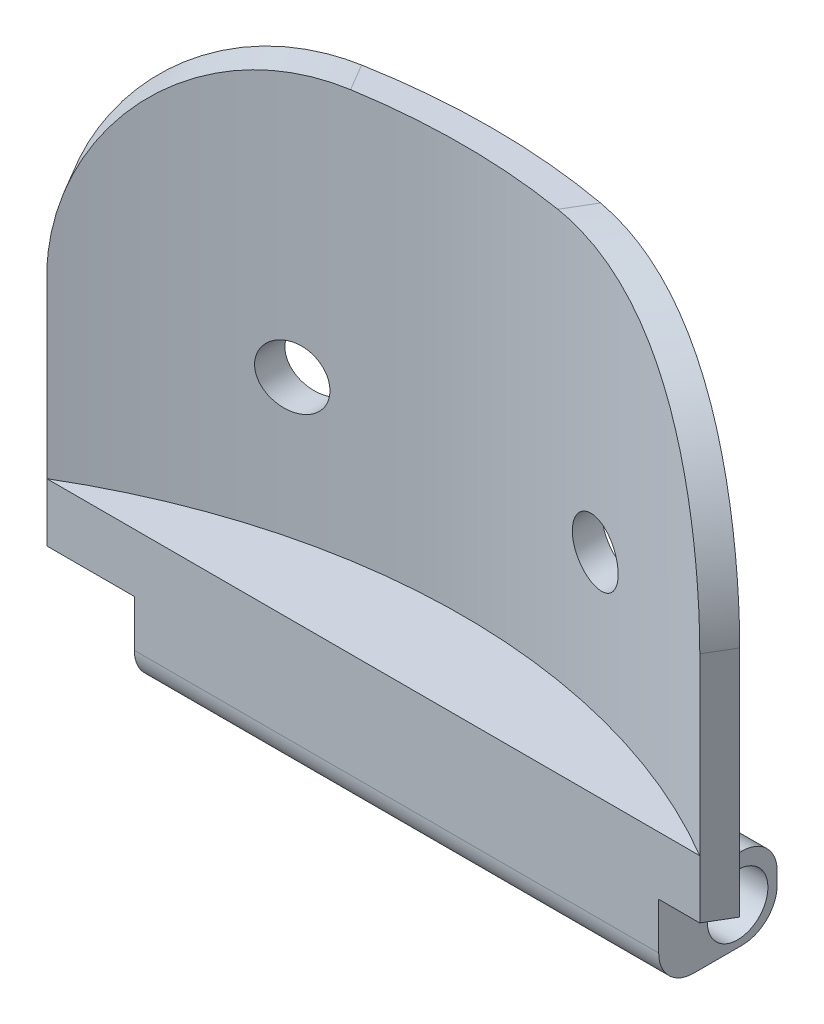
SolidWorks part; units mm, degrees
ref_plane "Front Plane" through (0, 0, 0) normal (0, 0, 1) x (1, 0, 0)
ref_plane "Top Plane" through (0, 0, 0) normal (0, 1, 0) x (1, 0, 0)
ref_plane "Right Plane" through (0, 0, 0) normal (1, 0, 0) x (0, 0, -1)
sketch "Sketch1" plane through (0, 0, 0) normal (0, 1, 0) x (1, 0, 0)
  line L2 (-37.2024, 62.8381) -> (-35.585, 60.106)
  line L3 (37.2024, 62.8381) -> (35.585, 60.106)
  circle A0 centre (0, 0) radius 73.025
  circle A1 centre (0, 0) radius 69.85
  point P7 (0, 62.8381)
extrude "Boss-Extrude1" add sketch "Sketch1" along normal blind 50.8 contours A1 L3 A0 L2 region at (0, 0, -72.2698)
fillet "Fillet1" radius 25.4 2 edges at (-36.3937, 50.8, -61.4721) (36.3937, 50.8, -61.4721)
sketch "Sketch2" plane through (0, 0, 0) normal (0, -1, 0) x (1, 0, 0)
  line L0 (0, -73.025) -> (0, -65.405) construction
  line L1 (25.4114, -73.025) -> (-25.3886, -73.025) construction
  line L2 (-25.3886, -73.025) -> (25.4114, -73.025)
  line L3 (-25.3886, -73.025) -> (-25.3886, -64.135)
  line L4 (25.4114, -73.025) -> (25.4114, -64.135)
  line L5 (-25.3886, -64.135) -> (25.4114, -64.135)
  arc A0 (-37.2024, -62.8381) -> (37.2024, -62.8381) centre (0, 0) ccw construction
  point P8 (0.0114, -73.025)
ref_plane "Plane1" through (0, 0, -73.025) normal (0, 0, -1) x (-1, 0, 0)
sketch "Sketch5" plane through (0, 0, -73.025) normal (0, 0, -1) x (-1, 0, 0)
  line L1 (16.51, 21.59) -> (-16.51, 21.59) construction
  circle A0 centre (-16.51, 21.59) radius 3.302
  circle A1 centre (16.51, 21.59) radius 3.302
  point P5 (0, 21.59)
extrude "Cut-Extrude2" cut sketch "Sketch5" against normal blind 17.78
ref_plane "Plane2" through (0, 0, -60.106) normal (0, 0, 1) x (1, 0, 0)
sketch "Sketch8" plane through (0, 0, -60.106) normal (0, 0, 1) x (1, 0, 0)
  line L0 (35.585, 0) -> (-35.585, 0)
  line L1 (35.585, 0) -> (35.585, 6.35)
  line L2 (-35.585, 0) -> (-35.585, 6.35)
  line L3 (35.585, 6.35) -> (-35.585, 6.35)
extrude "Boss-Extrude3" add sketch "Sketch8" against normal up to surface up to face at (19.7237, 22.3484, -67.0074)
sketch "Sketch10" plane through (0, 0, 0) normal (0, -1, 0) x (1, 0, 0)
  line L12 (0, -73.025) -> (37.2024, -73.025) construction
  line L13 (37.2024, -73.025) -> (37.2024, -62.8381) construction
  line L14 (37.2024, -73.025) -> (37.2024, -62.8381) construction
  line L15 (37.2024, -73.025) -> (-26.0436, -73.025) construction
  line L17 (-26.0436, -73.025) -> (-26.0436, -62.8381) construction
  line L18 (-26.0436, -60.106) -> (-20.0621, -60.106) construction
  line L19 (-35.585, -60.106) -> (35.585, -60.106) construction
  line L20 (-26.0436, -62.8381) -> (-26.0436, -60.106) construction
  line L21 (-26.0436, -62.8381) -> (37.2024, -62.8381) construction
  line L22 (-26.0436, -60.106) -> (37.2024, -60.106) construction
  line L23 (37.2024, -62.8381) -> (37.2024, -60.106) construction
  line L24 (-26.0436, -60.106) -> (-26.0436, -73.025)
  line L25 (-26.0436, -60.106) -> (31.1064, -60.106)
  line L26 (-26.0436, -73.025) -> (31.1064, -73.025)
  line L27 (31.1064, -60.106) -> (31.1064, -73.025)
  arc A0 (-37.2024, -62.8381) -> (37.2024, -62.8381) centre (0, 0) ccw construction
  arc M8 (-37.2024, -62.8381) -> (37.2024, -62.8381) centre (0, 0) ccw
extrude "Boss-Extrude5" add sketch "Sketch10" along normal blind 8.89 contours L21 L17 M8 | L15 L14 M8 | L17 L15 M8 region at (1.627, 0, -65.74) region at (-19.5762, 0, -71.5929) region at (23.4059, 0, -70.9563)
sketch "Sketch15" plane through (31.1064, 0, 0) normal (1, 0, 0) x (0, 0, -1)
  line L0 (73.025, -8.89) -> (68.707, -8.89) construction
  line L2 (60.106, -8.89) -> (73.025, -8.89) construction
  line L3 (68.707, -8.89) -> (68.707, -4.826) construction
  circle A1 centre (68.707, -4.826) radius 3.302
extrude "Cut-Extrude6" cut sketch "Sketch15" against normal blind 57.15
fillet "Fillet2" radius 3.81 4 edges at (-13.0218, 0, -73.025) (2.5314, -8.89, -60.106) (2.5314, -8.89, -73.025) (15.5532, 0, -73.025)
